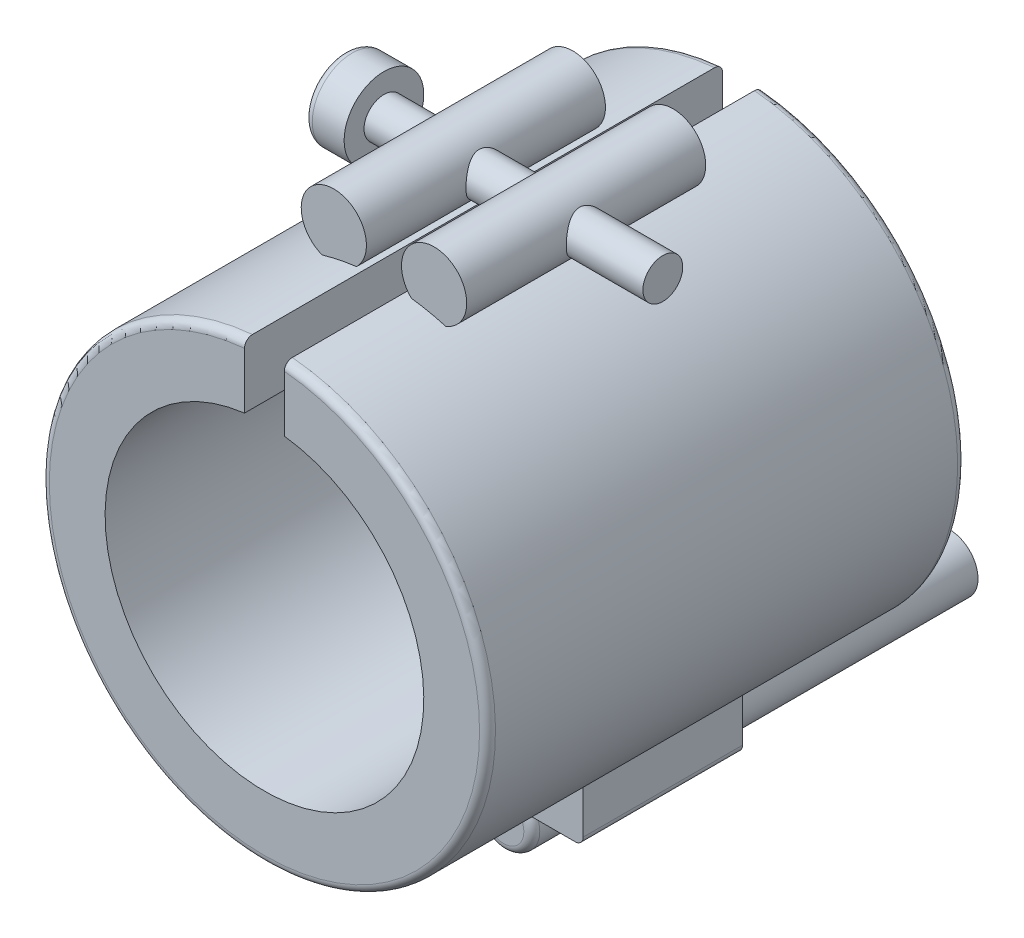
SolidWorks part; units mm, degrees
ref_plane "Front Plane" through (0, 0, 0) normal (0, 0, 1) x (1, 0, 0)
ref_plane "Top Plane" through (0, 0, 0) normal (0, 1, 0) x (1, 0, 0)
ref_plane "Right Plane" through (0, 0, 0) normal (1, 0, 0) x (0, 0, -1)
sketch "Sketch1" plane through (0, 0, 0) normal (0, 0, 1) x (1, 0, 0)
  line L0 (-2.5, 27.8882) -> (-2.5, 19.8431)
  line L1 (0, 0) -> (0, 34.2254) construction
  line L2 (2.5, 27.8882) -> (2.5, 19.8431)
  arc A0 (-2.5, 27.8882) -> (2.5, 27.8882) centre (0, 0) ccw
  arc A1 (-2.5, 19.8431) -> (2.5, 19.8431) centre (0, 0) ccw
  dimension "D1" = 40
  dimension "D2" = 8
  dimension "D3" = 5
extrude "Boss-Extrude1" add sketch "Sketch1" along normal mid plane 60
sketch "Sketch2" plane through (0, 0, 0) normal (0, 0, 1) x (1, 0, 0)
  line L0 (0, 0) -> (0, 40.0287) construction
  circle A0 centre (6.2935, 30.7225) radius 4.0912
  circle A1 centre (-6.2935, 30.7225) radius 4.0912
  arc A2 (-2.5, 27.8882) -> (2.5, 27.8882) centre (0, 0) ccw construction
  arc A3 (-2.5, 27.8882) -> (2.5, 27.8882) centre (0, 0) ccw construction
  dimension "D1" = 2.8343
  dimension "D3" = 8.1825
  dimension "D2" = 12.5871
extrude "Boss-Extrude2" add sketch "Sketch2" along normal mid plane 30
sketch "Sketch3" plane through (0, 0, 0) normal (0, 0, 1) x (1, 0, 0)
  line L0 (0, 0) -> (0, -23.0171) construction
  line L1 (-10, -23.0171) -> (10, -23.0171)
  line L2 (-10, -23.0171) -> (-10, -36)
  line L3 (-10, -36) -> (10, -36)
  line L4 (10, -23.0171) -> (10, -36)
  arc A0 (-2.5, 27.8882) -> (2.5, 27.8882) centre (0, 0) ccw construction
  dimension "D2" = 36
  dimension "D1" = 20
extrude "Boss-Extrude3" add sketch "Sketch3" against normal blind 20
sketch "Sketch4" plane through (0, 0, 0) normal (0, 0, 1) x (1, 0, 0)
  circle A0 centre (0, -38.1274) radius 3.5547
extrude "Boss-Extrude4" add sketch "Sketch4" against normal blind 56
fillet "Fillet1" radius 1 7 edges at (0, -28, -30) (0, -28, 30) (10, -26.1534, -10) (-10, -26.1534, -10) (-10, -36, -10) (10, -36, -10) (0, -41.6821, 0)
sketch "Sketch5" plane through (0, 0, 0) normal (1, 0, 0) x (0, 0, -1)
  circle A0 centre (0, 30.7225) radius 2.5
  dimension "D1" = 5
extrude "Boss-Extrude5" add sketch "Sketch5" along normal blind 20 and the other way blind 20
sketch "Sketch6" plane through (-20, 0, 0) normal (-1, 0, 0) x (0, 0, 1)
  circle A0 centre (0, 30.7225) radius 5
  circle A1 centre (0, 30.7225) radius 2.5 construction
  dimension "D1" = 10
extrude "Boss-Extrude6" add sketch "Sketch6" against normal blind 5
sketch "Sketch7" plane through (-20, 0, 0) normal (-1, 0, 0) x (0, 0, 1)
  line L1 (1.5877, 27.9725) -> (3.1754, 30.7225)
  line L2 (3.1754, 30.7225) -> (1.5877, 33.4725)
  line L3 (1.5877, 33.4725) -> (-1.5877, 33.4725)
  line L4 (-1.5877, 33.4725) -> (-3.1754, 30.7225)
  line L5 (-3.1754, 30.7225) -> (-1.5877, 27.9725)
  line L6 (-1.5877, 27.9725) -> (1.5877, 27.9725)
  circle A0 centre (0, 30.7225) radius 2.75 construction
  circle A1 centre (0, 30.7225) radius 5 construction
  point P10 (0, 27.9725)
  dimension "D1" = 5.5
extrude "Cut-Extrude1" cut sketch "Sketch7" against normal blind 3
fillet "Fillet2" radius 1 1 edges at (-20, 30.7225, 5)
